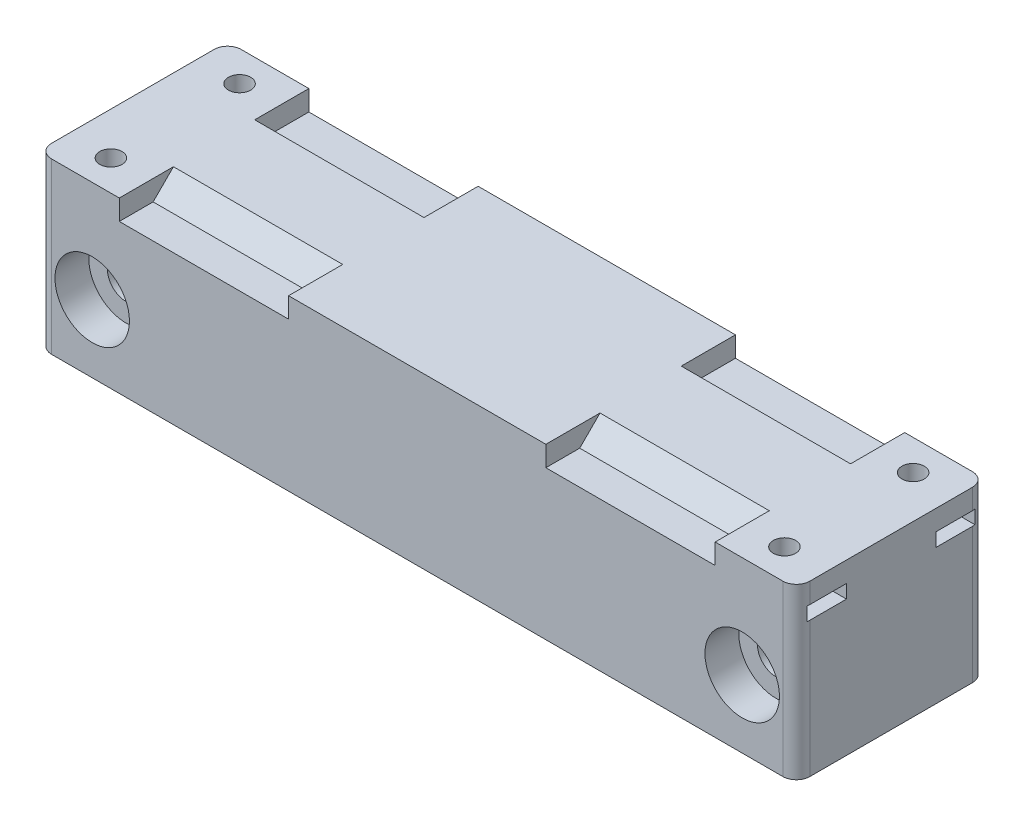
SolidWorks part; units mm, degrees
ref_plane "Front Plane" through (0, 0, 0) normal (0, 0, 1) x (1, 0, 0)
ref_plane "Top Plane" through (0, 0, 0) normal (0, 1, 0) x (1, 0, 0)
ref_plane "Right Plane" through (0, 0, 0) normal (1, 0, 0) x (0, 0, -1)
sketch "Sketch1" plane through (0, 0, 0) normal (0, 0, 1) x (1, 0, 0)
  line L8 (-56, 25) -> (-56, 0)
  line L9 (-56, 0) -> (0, 0)
  line L10 (0, -1055) -> (0, 0) construction
  line L12 (-56, 25) -> (0, 25)
  line L13 (0, 0) -> (0, 72.4167) construction
  line L14 (0, 25) -> (0, 0)
  dimension "D1" = 25
  dimension "D4" = 112
extrude "Boss-Extrude1" add sketch "Sketch1" along normal mid plane 28
hole_wizard "CBORE for M5 Hex Head Bolt1" positions "Sketch2" profile "Sketch3" counterbore size "M5" standard "ANSI Metric" end condition through all
sketch "Sketch2" plane through (0, 0, 14) normal (0, 0, 1) x (1, 0, 0)
  line L0 (-56, 10) -> (0, 10) construction
  line L1 (-56, 25) -> (-56, 0) construction
  line L3 (-48, 25) -> (-48, 0) construction
  line L5 (-56, 0) -> (0, 0) construction
  line L8 (0, 25) -> (-56, 25) construction
  line L10 (-56, 25) -> (-56, 0) construction
  point P0 (-48, 10)
  point P17 (-52.1787, 10)
  point P18 (-52, 10)
  point P19 (-48, 20)
  point P20 (-48, 25.519)
  point P21 (-48, 25)
  point P24 (-48, 12.5)
  point P25 (-48, 12.5)
  point P26 (-48, 25)
  point P29 (0, 0)
  point P30 (-48, 21.2922)
  point P33 (0, 0)
  point P34 (-48, 12.5)
  point P35 (-48, 12.5)
  point P36 (-56, 12.5)
  point P39 (-48, 10)
  point P40 (-56, 10)
  point P43 (0, 10)
  dimension "D1" = 8
  dimension "D2" = 10
sketch "Sketch3" plane through (-48, 10, 14) normal (1, 0, 0) x (0, -1, 0)
  line L0 (0, 0) -> (0, 28)
  line L1 (0, 28) -> (2.75, 28)
  line L3 (2.75, 28) -> (2.75, 5)
  line L4 (2.75, 5) -> (5.5, 5)
  line L5 (5.5, 5) -> (5.5, 0)
  line L7 (5.5, 0) -> (0, 0)
  line L11 (0, -6.35) -> (0, 107.95) construction
  dimension "Thru Hole Dia." = 5.5
  dimension "Thru Hole Depth" = 28
  dimension "C'Bore Dia." = 11
  dimension "C'Bore Depth" = 5
sketch "Sketch9" plane through (0, 25, 0) normal (0, 1, 0) x (1, 0, 0)
  line L0 (0, 14) -> (-56, 14) construction
  line L1 (-44, 6) -> (-19, 6)
  line L2 (-44, 6) -> (-44, 14)
  line L3 (-44, 14) -> (-19, 14)
  line L4 (-19, 6) -> (-19, 14)
  line L5 (-44, 6) -> (-19, 14) construction
  line L6 (-44, 14) -> (-19, 6) construction
  line L7 (0, -14) -> (-56, -14) construction
  line L8 (-19, -6) -> (-44, -6)
  line L9 (-19, -6) -> (-19, -14)
  line L10 (-19, -14) -> (-44, -14)
  line L11 (-44, -6) -> (-44, -14)
  line L12 (-19, -6) -> (-44, -14) construction
  line L13 (-19, -14) -> (-44, -6) construction
  line L14 (-56, -14) -> (-56, 14) construction
  line L15 (-44, -6) -> (-44, 6) construction
  point P0 (-31.5, 10)
  point P7 (-31.5, -10)
  dimension "D1" = 8
  dimension "D2" = 25
  dimension "D3" = 12
extrude "Cut-Extrude2" cut sketch "Sketch9" against normal blind 3
sketch "Sketch8" plane through (-56, 0, 0) normal (-1, 0, 0) x (0, 0, 1)
  line L0 (0, 0) -> (0, 21) construction
  line L1 (-12.4, 20) -> (-6.6, 20)
  line L2 (-12.4, 20) -> (-12.4, 22)
  line L3 (-12.4, 22) -> (-6.6, 22)
  line L4 (-6.6, 20) -> (-6.6, 22)
  line L5 (-12.4, 20) -> (-6.6, 22) construction
  line L6 (-12.4, 22) -> (-6.6, 20) construction
  line L7 (6.6, 20) -> (12.4, 20)
  line L8 (6.6, 20) -> (6.6, 22)
  line L9 (6.6, 22) -> (12.4, 22)
  line L10 (12.4, 20) -> (12.4, 22)
  line L11 (6.6, 20) -> (12.4, 22) construction
  line L12 (6.6, 22) -> (12.4, 20) construction
  line L13 (14, 0) -> (-14, 0) construction
  line L14 (-9.5, 21) -> (9.5, 21) construction
  line L15 (14, 25) -> (-14, 25) construction
  point P0 (-9.5, 21)
  point P5 (9.5, 21)
  point P16 (0, 21.4522)
  point P17 (0, 0)
  dimension "D1" = 5.8
  dimension "D2" = 19
  dimension "D3" = 2
  dimension "D4" = 4
extrude "Cut-Extrude1" cut sketch "Sketch8" against normal blind 10
chamfer "Chamfer1" [suppressed] distance 3 angle 30
mirror "Mirror1" about plane through (0, 25, 14) normal (-1, 0, 0) of bodies 113 109
hole_wizard "Ø3.0mm Dowel Hole1" positions "Sketch6" profile "Sketch7" hole size "Ø3.0" standard "ANSI Metric"
sketch "Sketch6" plane through (0, 25, 0) normal (0, 1, 0) x (1, 0, 0)
  line L1 (-49.74, -9.5) -> (49.74, -9.5) construction
  line L2 (-49.74, -9.5) -> (-49.74, 9.5) construction
  line L3 (-49.74, 9.5) -> (49.74, 9.5) construction
  line L4 (49.74, -9.5) -> (49.74, 9.5) construction
  line L5 (-49.74, -9.5) -> (49.74, 9.5) construction
  line L6 (-49.74, 9.5) -> (49.74, -9.5) construction
  point P4 (49.74, 9.5)
  point P63 (-49.74, -9.5)
  point P64 (-49.74, 9.5)
  point P65 (49.74, -9.5)
  dimension "D1" = 99.48
  dimension "D2" = 19
sketch "Sketch7" plane through (49.74, 25, -9.5) normal (1, 0, 0) x (0, 0, 1)
  line L0 (0, 0) -> (0, 8.9914)
  line L1 (0, 8.9914) -> (1.65, 8)
  line L2 (1.65, 8) -> (1.65, 0)
  line L5 (1.65, 0) -> (0, 0)
  line L10 (0, 8.9914) -> (-1.65, 8) construction
  line L11 (0, -6.35) -> (0, 107.95) construction
  dimension "Hole Dia." = 3.3
  dimension "Hole Depth" = 8
  dimension "Drill Angle" = 118
fillet "Fillet1" radius 2 4 edges at (-56, 12.5, -14) (-56, 12.5, 14) (56, 12.5, -14) (56, 12.5, 14)
chamfer "Chamfer2" distance 3 angle 45 4 edges at (-31.5, 22, 6) (31.5, 22, 6) (-31.5, 22, -6) (31.5, 22, -6)
